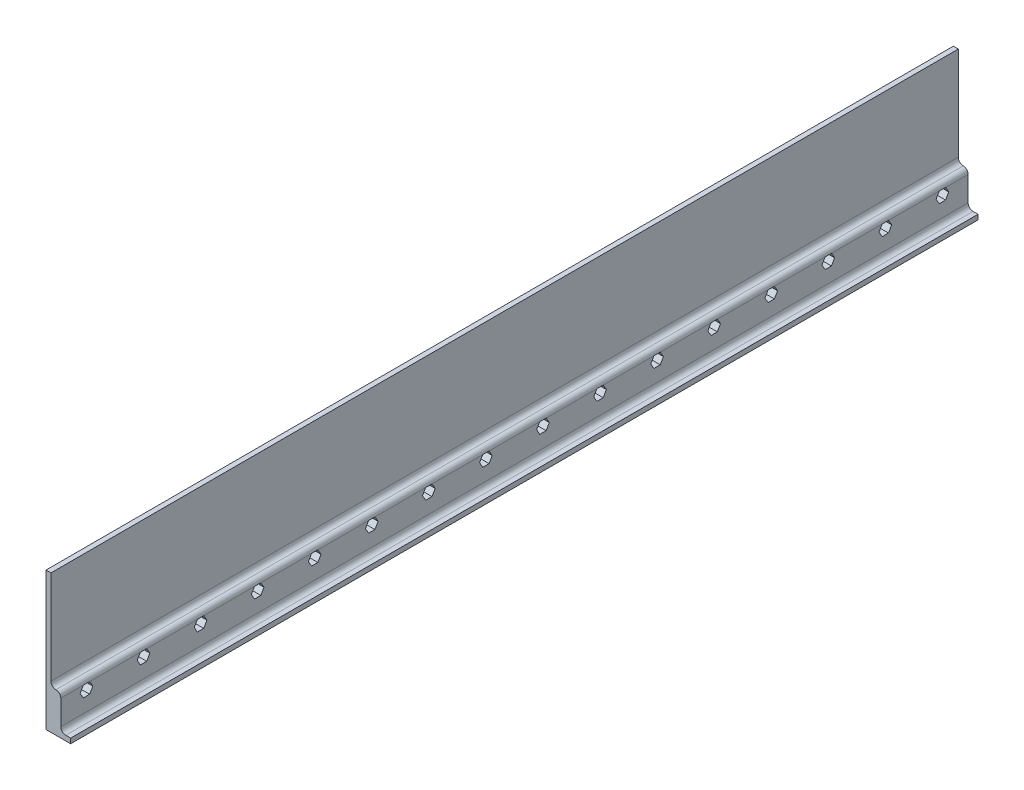
SolidWorks part; units mm, degrees
material "AISI 4340 Steel, annealed"
ref_plane "Front Plane" through (0, 0, 0) normal (0, 0, 1) x (1, 0, 0)
ref_plane "Top Plane" through (0, 0, 0) normal (0, 1, 0) x (1, 0, 0)
ref_plane "Right Plane" through (0, 0, 0) normal (1, 0, 0) x (0, 0, -1)
sketch "Sketch2" plane through (0, 0, 0) normal (0, 0, 1) x (1, 0, 0)
  line L0 (-12.5, 20) -> (12.5, -20) construction
  line L5 (-12.5, -20) -> (12.5, 20) construction
  line L6 (-12.5, 20) -> (-12.5, -20)
  line L7 (-12.5, -20) -> (12.5, -20)
  line L8 (12.5, -20) -> (12.5, -15)
  line L9 (12.5, -15) -> (2.5, -15)
  line L10 (2.5, -15) -> (2.5, 20)
  line L11 (2.5, 20) -> (-12.5, 20)
  point P4 (0, 0)
  point P6 (0, 0)
  dimension "D1" = 25
  dimension "D2" = 40
  dimension "D3" = 15
  dimension "D4" = 5
extrude "General extrude" add sketch "Sketch2" along normal mid plane 919.52
fillet "Rounding" radius 5 2 edges at (2.5, 20, 0) (2.5, -15, 0)
sketch "Sketch3" plane through (-12.5, 0, 0) normal (-1, 0, 0) x (0, 0, 1)
  line L0 (459.76, -20) -> (-459.76, -20) construction
  line L211 (436.9672, 3.89) -> (440.1744, 9.445)
  line L212 (379.1372, 3.89) -> (382.3444, 9.445)
  line L213 (382.3444, 9.445) -> (379.1372, 15)
  line L214 (440.1744, 9.445) -> (436.9672, 15)
  line L215 (379.1372, 15) -> (372.7228, 15)
  line L216 (436.9672, 15) -> (430.5528, 15)
  line L217 (430.5528, 15) -> (427.3456, 9.445)
  line L218 (427.3456, 9.445) -> (430.5528, 3.89)
  line L219 (430.5528, 3.89) -> (436.9672, 3.89)
  line L220 (459.76, 20) -> (-459.76, 20) construction
  line L695 (372.7228, 15) -> (369.5156, 9.445)
  line L696 (369.5156, 9.445) -> (372.7228, 3.89)
  line L697 (372.7228, 3.89) -> (379.1372, 3.89)
  line L698 (321.3072, 3.89) -> (324.5144, 9.445)
  line L699 (324.5144, 9.445) -> (321.3072, 15)
  line L700 (321.3072, 15) -> (314.8928, 15)
  line L701 (314.8928, 15) -> (311.6856, 9.445)
  line L702 (311.6856, 9.445) -> (314.8928, 3.89)
  line L703 (314.8928, 3.89) -> (321.3072, 3.89)
  line L704 (263.4772, 3.89) -> (266.6844, 9.445)
  line L705 (266.6844, 9.445) -> (263.4772, 15)
  line L706 (263.4772, 15) -> (257.0628, 15)
  line L707 (257.0628, 15) -> (253.8556, 9.445)
  line L708 (253.8556, 9.445) -> (257.0628, 3.89)
  line L709 (257.0628, 3.89) -> (263.4772, 3.89)
  line L710 (205.6472, 3.89) -> (208.8544, 9.445)
  line L711 (208.8544, 9.445) -> (205.6472, 15)
  line L712 (205.6472, 15) -> (199.2328, 15)
  line L713 (199.2328, 15) -> (196.0256, 9.445)
  line L714 (196.0256, 9.445) -> (199.2328, 3.89)
  line L715 (199.2328, 3.89) -> (205.6472, 3.89)
  line L716 (147.8172, 3.89) -> (151.0244, 9.445)
  line L717 (151.0244, 9.445) -> (147.8172, 15)
  line L718 (147.8172, 15) -> (141.4028, 15)
  line L719 (141.4028, 15) -> (138.1956, 9.445)
  line L720 (138.1956, 9.445) -> (141.4028, 3.89)
  line L721 (141.4028, 3.89) -> (147.8172, 3.89)
  line L722 (89.9872, 3.89) -> (93.1944, 9.445)
  line L723 (93.1944, 9.445) -> (89.9872, 15)
  line L724 (89.9872, 15) -> (83.5728, 15)
  line L725 (83.5728, 15) -> (80.3656, 9.445)
  line L726 (80.3656, 9.445) -> (83.5728, 3.89)
  line L727 (83.5728, 3.89) -> (89.9872, 3.89)
  line L728 (32.1572, 3.89) -> (35.3644, 9.445)
  line L729 (35.3644, 9.445) -> (32.1572, 15)
  line L730 (32.1572, 15) -> (25.7428, 15)
  line L731 (25.7428, 15) -> (22.5356, 9.445)
  line L732 (22.5356, 9.445) -> (25.7428, 3.89)
  line L733 (25.7428, 3.89) -> (32.1572, 3.89)
  line L734 (-25.6728, 3.89) -> (-22.4656, 9.445)
  line L735 (-22.4656, 9.445) -> (-25.6728, 15)
  line L736 (-25.6728, 15) -> (-32.0872, 15)
  line L737 (-32.0872, 15) -> (-35.2944, 9.445)
  line L738 (-35.2944, 9.445) -> (-32.0872, 3.89)
  line L739 (-32.0872, 3.89) -> (-25.6728, 3.89)
  line L740 (-83.5028, 3.89) -> (-80.2956, 9.445)
  line L741 (-80.2956, 9.445) -> (-83.5028, 15)
  line L742 (-83.5028, 15) -> (-89.9172, 15)
  line L743 (-89.9172, 15) -> (-93.1244, 9.445)
  line L744 (-93.1244, 9.445) -> (-89.9172, 3.89)
  line L745 (-89.9172, 3.89) -> (-83.5028, 3.89)
  line L746 (-141.3328, 3.89) -> (-138.1256, 9.445)
  line L747 (-138.1256, 9.445) -> (-141.3328, 15)
  line L748 (-141.3328, 15) -> (-147.7472, 15)
  line L749 (-147.7472, 15) -> (-150.9544, 9.445)
  line L750 (-150.9544, 9.445) -> (-147.7472, 3.89)
  line L751 (-147.7472, 3.89) -> (-141.3328, 3.89)
  line L752 (-199.1628, 3.89) -> (-195.9556, 9.445)
  line L753 (-195.9556, 9.445) -> (-199.1628, 15)
  line L754 (-199.1628, 15) -> (-205.5772, 15)
  line L755 (-205.5772, 15) -> (-208.7844, 9.445)
  line L756 (-208.7844, 9.445) -> (-205.5772, 3.89)
  line L757 (-205.5772, 3.89) -> (-199.1628, 3.89)
  line L758 (-256.9928, 3.89) -> (-253.7856, 9.445)
  line L759 (-253.7856, 9.445) -> (-256.9928, 15)
  line L760 (-256.9928, 15) -> (-263.4072, 15)
  line L761 (-263.4072, 15) -> (-266.6144, 9.445)
  line L762 (-266.6144, 9.445) -> (-263.4072, 3.89)
  line L763 (-263.4072, 3.89) -> (-256.9928, 3.89)
  line L764 (-314.8228, 3.89) -> (-311.6156, 9.445)
  line L765 (-311.6156, 9.445) -> (-314.8228, 15)
  line L766 (-314.8228, 15) -> (-321.2372, 15)
  line L767 (-321.2372, 15) -> (-324.4444, 9.445)
  line L768 (-324.4444, 9.445) -> (-321.2372, 3.89)
  line L769 (-321.2372, 3.89) -> (-314.8228, 3.89)
  line L770 (-372.6528, 3.89) -> (-369.4456, 9.445)
  line L771 (-369.4456, 9.445) -> (-372.6528, 15)
  line L772 (-372.6528, 15) -> (-379.0672, 15)
  line L773 (-379.0672, 15) -> (-382.2744, 9.445)
  line L774 (-382.2744, 9.445) -> (-379.0672, 3.89)
  line L775 (-379.0672, 3.89) -> (-372.6528, 3.89)
  line L776 (-430.4828, 3.89) -> (-427.2756, 9.445)
  line L777 (-427.2756, 9.445) -> (-430.4828, 15)
  line L778 (-430.4828, 15) -> (-436.8972, 15)
  line L779 (-436.8972, 15) -> (-440.1044, 9.445)
  line L780 (-440.1044, 9.445) -> (-436.8972, 3.89)
  line L781 (-436.8972, 3.89) -> (-430.4828, 3.89)
  circle A0 centre (433.76, 9.445) radius 5.555 construction
  dimension "D1" = 11.11
  dimension "D2" = 5
  dimension "D3" = 26
extrude "Roller holders" cut sketch "Sketch3" against normal through all
sketch "Sketch5" plane through (0, 20, 0) normal (0, 1, 0) x (1, 0, 0)
  line L0 (-2.5, -459.76) -> (-12.5, -459.76) construction
  line L1 (-12.5, 459.76) -> (-7.5, 459.76)
  line L2 (-12.5, 459.76) -> (-12.5, -459.76)
  line L3 (-12.5, -459.76) -> (-7.5, -459.76)
  line L4 (-7.5, 459.76) -> (-7.5, -459.76)
  dimension "D1" = 5
extrude "Guard rail" add sketch "Sketch5" along normal blind 100
fillet "Guard rail support fillet" radius 5 1 edges at (-7.5, 20, 0)
